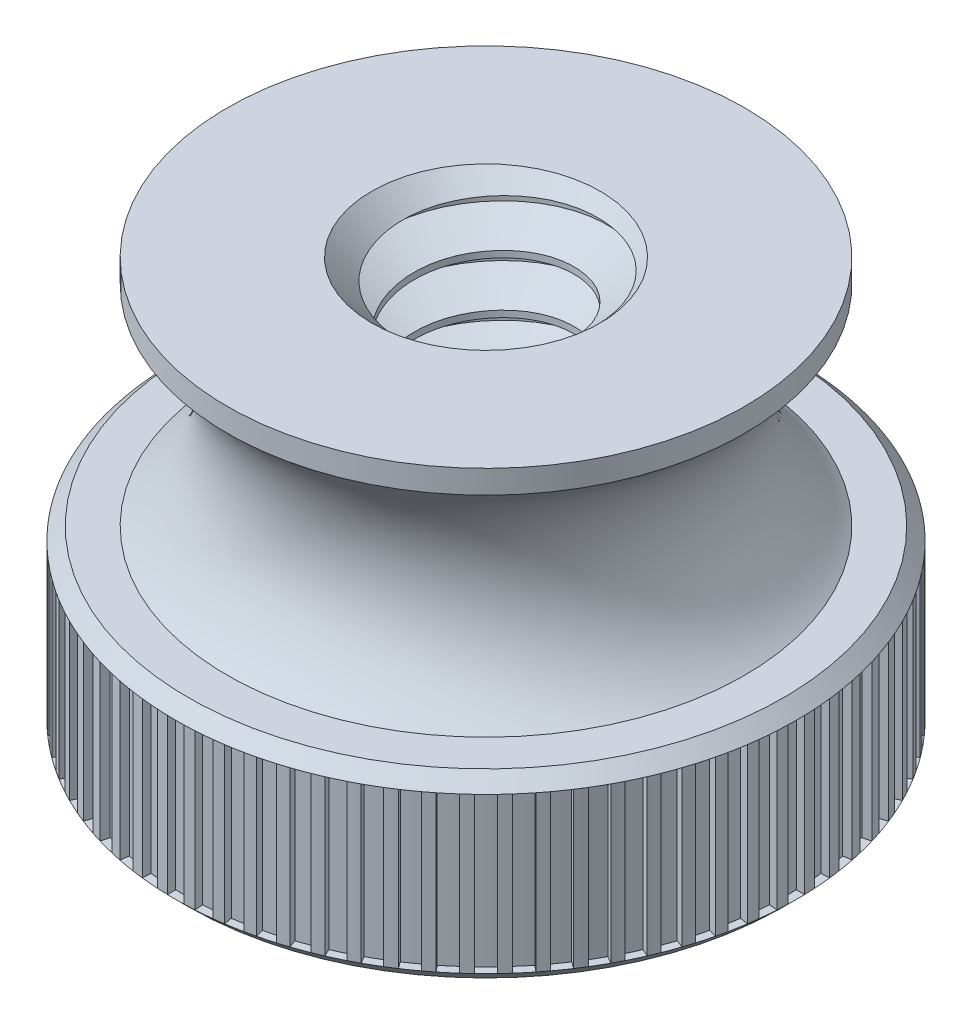
SolidWorks part; units mm, degrees
ref_plane "Front Plane" through (0, 0, 0) normal (0, 0, 1) x (1, 0, 0)
ref_plane "Top Plane" through (0, 0, 0) normal (0, 1, 0) x (1, 0, 0)
ref_plane "Right Plane" through (0, 0, 0) normal (1, 0, 0) x (0, 0, -1)
sketch "Sketch1" plane through (0, 0, 0) normal (0, 0, 1) x (1, 0, 0)
  line L0 (0, 0) -> (0, 6.35) construction
  line L1 (0, 6.35) -> (-3.9688, 6.35)
  line L2 (-4.7625, 2.7781) -> (-4.7625, 0)
  line L3 (-4.7625, 0) -> (0, 0)
  line L4 (0, 0) -> (0, 6.35)
  line L5 (0, 0) -> (0, -2.6189) construction
  line L6 (-3.175, 2.7781) -> (-3.175, 6.35) construction
  line L7 (-4.7625, 2.7781) -> (-3.9688, 2.7781)
  line L10 (-3.9688, 6.35) -> (-3.9688, 5.9928)
  arc A0 (-3.9688, 2.7781) -> (-3.9688, 5.9928) centre (-5.1993, 4.3855) ccw
  point P1 (0, 3.175)
  dimension "D1" = 0.3572
  dimension "D2" = 0.7937
revolve "Revolve1" add sketch "Sketch1" angle 360 about L0
sketch "Sketch3" plane through (0, 0, 0) normal (0, 1, 0) x (1, 0, 0)
  circle A0 centre (0, 0) radius 1.7526
extrude "Cut-Extrude1" cut sketch "Sketch3" along normal through all
sketch "Sketch4" plane through (0, 0, 0) normal (0, 1, 0) x (1, 0, 0)
  circle A1 centre (0, 0) radius 1.7526
  circle A2 centre (0, 0) radius 1.7526
  dimension "D1" = 0
curve "Helix/Spiral1" pitch 0.7937 height 12.7 turns 16 parameters "pitch"=0.7937
sketch "Sketch21" plane through (0, 0, 0) normal (0, 1, 0) x (1, 0, 0)
  line L0 (0, 1.7526) -> (0, 4.7625)
  circle A0 centre (0, 0) radius 4.7625 construction
  circle A1 centre (0, 0) radius 1.7526 construction
  circle A2 centre (0, 0) radius 4.7625 construction
  circle A3 centre (0, 0) radius 1.7526 construction
  dimension "D1" = 3.0099
sketch "Sketch5" plane through (0, 0, 0) normal (1, 0, 0) x (0, 0, -1)
  line L0 (-1.7526, 0) -> (-1.7526, -0.6945)
  line L1 (-1.7526, -0.6945) -> (-1.237, -0.3969)
  line L2 (-1.237, -0.3969) -> (-1.237, -0.2977)
  line L3 (-1.237, -0.2977) -> (-1.7526, 0)
  line L4 (-1.237, -0.3473) -> (-1.7526, -0.3473) construction
  line L5 (-1.4948, -0.5457) -> (-1.4948, -0.1488) construction
  line L6 (1.7526, 0) -> (-1.7526, 0) construction
  dimension "D1" = 0.0992
  dimension "D2" = 0.3969
  dimension "D3" = 60
sweep "Sweep1" add profiles "Sketch5" path "Helix/Spiral1"
sketch "Sketch13" plane through (0, 0, 0) normal (0, -1, 0) x (1, 0, 0)
  circle A1 centre (0, 0) radius 4.7625
  circle A2 centre (0, 0) radius 4.7625
  dimension "D1" = 0
extrude "Cut-Extrude2" cut sketch "Sketch13" along normal through all
sketch "Sketch14" plane through (0, 6.35, 0) normal (0, 1, 0) x (1, 0, 0)
  circle A0 centre (0, 0) radius 4.7625 construction
  circle A1 centre (0, 0) radius 4.7625
extrude "Cut-Extrude3" cut sketch "Sketch14" along normal through all
sketch "Sketch15" plane through (0, 0, 0) normal (0, -1, 0) x (1, 0, 0)
  circle A0 centre (0, 0) radius 1.7526 construction
  circle A1 centre (0, 0) radius 1.7526
extrude "Cut-Extrude4" cut sketch "Sketch15" against normal through all draft 45
sketch "Sketch16" plane through (0, 6.35, 0) normal (0, 1, 0) x (1, 0, 0)
  circle A0 centre (0, 0) radius 1.7526 construction
  circle A1 centre (0, 0) radius 1.7526
extrude "Cut-Extrude5" cut sketch "Sketch16" against normal through all draft 45
chamfer "Chamfer1" distance 0.1984 angle 45 2 edges at (0, 2.7781, -4.7625) (0, 0, -4.7625)
sketch "Sketch11" plane through (0, 0, 0) normal (0, 0, 1) x (1, 0, 0)
  line L0 (-1.7526, 6.35) -> (-1.7526, 0)
  line L1 (1.7526, 6.35) -> (1.7526, 0)
  line L2 (3.9688, 6.35) -> (-3.9688, 6.35) construction
  line L4 (-1.7526, 0) -> (1.7526, 0) construction
  dimension "D1" = 3.5052
sketch "Sketch12" plane through (0, 0, 0) normal (1, 0, 0) x (0, 0, -1)
  line L0 (-1.7526, 6.35) -> (-1.7526, 0)
  line L1 (1.7526, 6.35) -> (1.7526, 0)
  line L2 (-1.7526, 0) -> (1.7526, 0) construction
  line L3 (3.9688, 6.35) -> (-3.9688, 6.35) construction
  line L5 (-4.5641, 0) -> (4.5641, 0) construction
  dimension "D1" = 3.5052
ref_plane "Plane1" through (0, 0, -12.7) normal (0, 0, 1) x (1, 0, 0)
sketch "Sketch17" plane through (0, 0, -12.7) normal (0, 0, 1) x (1, 0, 0)
  line L0 (-0.127, 0.1984) -> (-0.127, 2.5797)
  line L1 (4.7625, 0.1984) -> (-4.7625, 0.1984) construction
  line L2 (4.7625, 2.5797) -> (-4.7625, 2.5797) construction
  line L3 (0.127, 0.1984) -> (0.127, 2.5797)
  line L4 (0, 0.1984) -> (0, 2.5797) construction
  line L5 (-0.127, 0.1984) -> (0.127, 0.1984)
  line L6 (-0.127, 2.5797) -> (0.127, 2.5797)
  line L7 (0, 1.3891) -> (6.048, 1.3891) construction
  line L8 (0, 1.3891) -> (0, 0) construction
  dimension "D1" = 0
  dimension "D2" = 0.254
extrude "Cut-Extrude6" cut sketch "Sketch17" along normal offset from surface (8.0662 mm away) 0.127 up to face at (0, 2.5797, -4.7625) offset beyond the face yes
pattern_circular "CirPattern1" count 72 over 360 about axis through (0, 0, 0) along (0, 1, 0) of "Cut-Extrude6"
sketch "Sketch18" plane through (0, 6.35, 0) normal (0, 1, 0) x (1, 0, 0)
  circle A0 centre (0, 0) radius 4.7625
  arc A2 (1.3549, 4.5657) -> (1.1095, 4.6315) centre (0, 0) ccw construction
ref_plane "Plane3" through (0, 3.175, 0) normal (0, 1, 0) x (-1, 0, 0)
equation "\"D1@Sketch5\" = \"pitch@Helix/Spiral1\"*.125"
equation "\"D2@Sketch5\" = \"pitch@Helix/Spiral1\"*.5"
equation "\"D1@Sketch11\" = \"OD@Sketch3\""
equation "\"D1@Sketch12\" = \"OD@Sketch3\""
equation "\"D1@Chamfer1\" = \"pitch@Helix/Spiral1\"*.25"
equation "\"D3@Helix/Spiral1\" = \"B@Sketch1\"+.250"
equation "\"D1@Sketch1\" = \"D@Sketch1\"/10"
equation "\"D2@Sketch1\" = \"C@Sketch1\"*.1"
